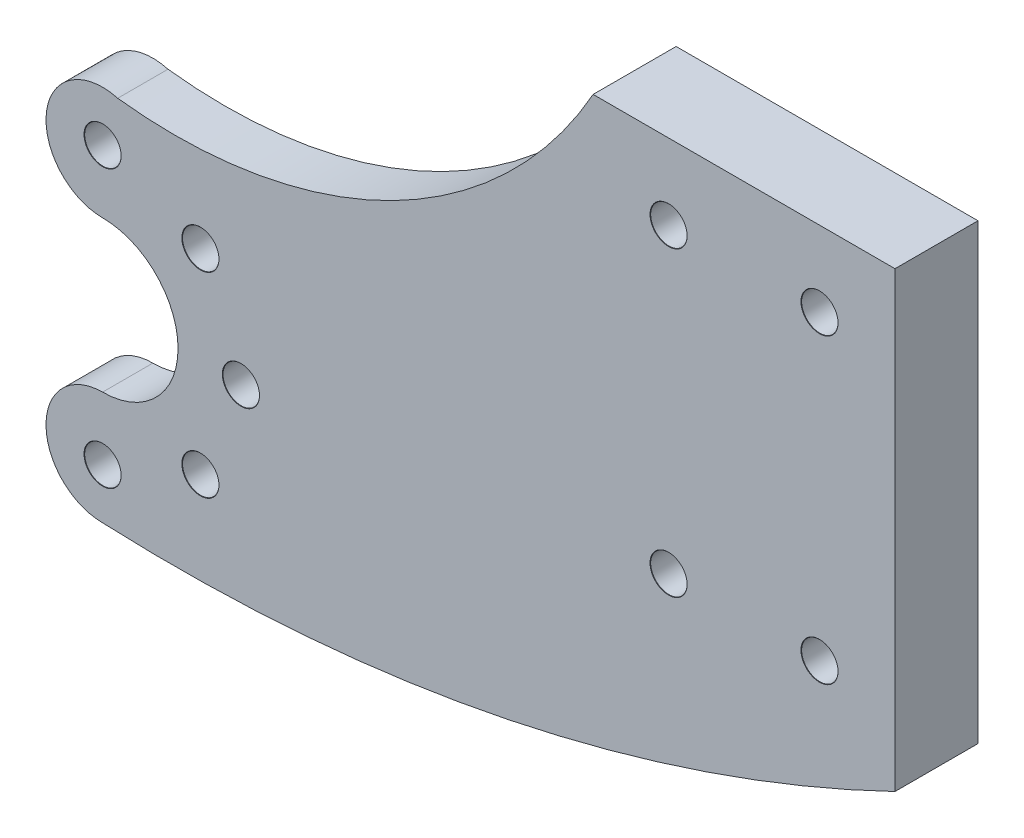
SolidWorks part; units mm, degrees
ref_plane "前视基准面" through (0, 0, 0) normal (0, 0, 1) x (1, 0, 0)
ref_plane "上视基准面" through (0, 0, 0) normal (0, 1, 0) x (1, 0, 0)
ref_plane "右视基准面" through (0, 0, 0) normal (1, 0, 0) x (0, 0, -1)
sketch "草图1" plane through (0, 0, 0) normal (0, 0, 1) x (1, 0, 0)
  line L1 (0, 0) -> (-24, 0)
  line L2 (0, 0) -> (0, 36)
  line L3 (0, 36) -> (-24, 36)
  line L4 (-24, 0) -> (-24, 36)
  dimension "D1" = 36
  dimension "D2" = 24
extrude "凸台-拉伸1" add sketch "草图1" along normal blind 2.6
sketch "草图4" plane through (0, 0, 2.6) normal (0, 0, 1) x (1, 0, 0)
  line L0 (-63, 16.999) -> (-63, -12.999)
  line L1 (-12, 36) -> (-12, 0) construction
  line L2 (-24, 36) -> (0, 36)
  line L3 (0, 36) -> (0, 0)
  line L4 (-63, 2) -> (-77.0817, 2) construction
  line L5 (-24, 18) -> (0, 18) construction
  line L6 (-24, 36) -> (-24, 0) construction
  line L7 (-63, 16.999) -> (-63, 8)
  line L8 (-63, -12.999) -> (-63, -4)
  arc A3 (-63, -12.999) -> (0, 0) centre (-57.2579, 118.3371) ccw
  arc A4 (-63, 16.999) -> (-24, 36) centre (-57.2497, 54.7211) ccw
  circle A5 centre (-63, 2) radius 6
  circle A6 centre (-63, 12.5) radius 4.499
  circle A7 centre (-63, -8.5) radius 4.499
  line M7 (0, 0) -> (0, 36)
  line M8 (0, 36) -> (-24, 36)
  line M9 (-24, 36) -> (-24, 0)
  line M10 (-24, 0) -> (0, 0)
  dimension "D4" = 16
  dimension "D6" = 12
  dimension "D3" = 51
extrude "凸台-拉伸2" add sketch "草图4" along normal blind 4 contours A5 L0 A3 A4 M10 M9 | M10 M7 M8 M9 | A6 | A7 region at (-38.1122, 4.6974, 2.6) region at (-12, 18, 2.6)
hole_wizard "M2.5 间隙孔2" positions "草图5" profile "草图6" hole size "M2.5" standard "ISO" end condition through all
sketch "草图5" plane through (0, 0, 6.6) normal (0, 0, 1) x (1, 0, 0)
  line L0 (-63, 2) -> (-63, 12.3527) construction
  circle A1 centre (-63, 2) radius 1.4731 construction
  point P14 (-63, 13)
  point P21 (-55.2218, 9.7782)
  point P22 (-52, 2)
  point P23 (-55.2218, -5.7782)
  point P24 (-63, -9)
  dimension "D1" = 11
  dimension "D2" = 5
sketch "草图6" plane through (-63, -9, 6.6) normal (1, 0, 0) x (0, -1, 0)
  line L0 (0, 0) -> (0, 6.6)
  line L1 (0, 6.6) -> (1.45, 6.6)
  line L2 (1.45, 6.6) -> (1.45, 0.025)
  line L3 (1.45, 0.025) -> (1.475, 0)
  line L5 (1.475, 0) -> (0, 0)
  line L6 (-1.45, 0.025) -> (-1.475, 0) construction
  line L11 (0, -6.35) -> (0, 107.95) construction
  dimension "通孔孔直径" = 2.9
  dimension "通孔孔深度" = 6.6
  dimension "近端锥形沉头孔直径" = 2.95
  dimension "近端锥形沉头孔角度" = 90
hole_wizard "M2.5 间隙孔1" positions "草图7" profile "草图8" hole size "M2.5" standard "ISO" end condition through all
sketch "草图7" plane through (0, 0, 6.6) normal (0, 0, 1) x (1, 0, 0)
  line L0 (-12, 36) -> (-12, -8.6488) construction
  line L3 (0, 18) -> (-41.4541, 18) construction
  point P17 (-18, 30)
  point P19 (-18, 6)
  point P21 (-6, 6)
  point P22 (-6, 30)
  dimension "D1" = 24
  dimension "D2" = 12
  dimension "D3" = 6
  dimension "D4" = 6
sketch "草图8" plane through (-6, 30, 6.6) normal (1, 0, 0) x (0, -1, 0)
  line L0 (0, 0) -> (0, 6.6)
  line L1 (0, 6.6) -> (1.45, 6.6)
  line L2 (1.45, 6.6) -> (1.45, 0.025)
  line L3 (1.45, 0.025) -> (1.475, 0)
  line L5 (1.475, 0) -> (0, 0)
  line L6 (-1.45, 0.025) -> (-1.475, 0) construction
  line L11 (0, -6.35) -> (0, 107.95) construction
  dimension "通孔孔直径" = 2.9
  dimension "通孔孔深度" = 6.6
  dimension "近端锥形沉头孔直径" = 2.95
  dimension "近端锥形沉头孔角度" = 90
